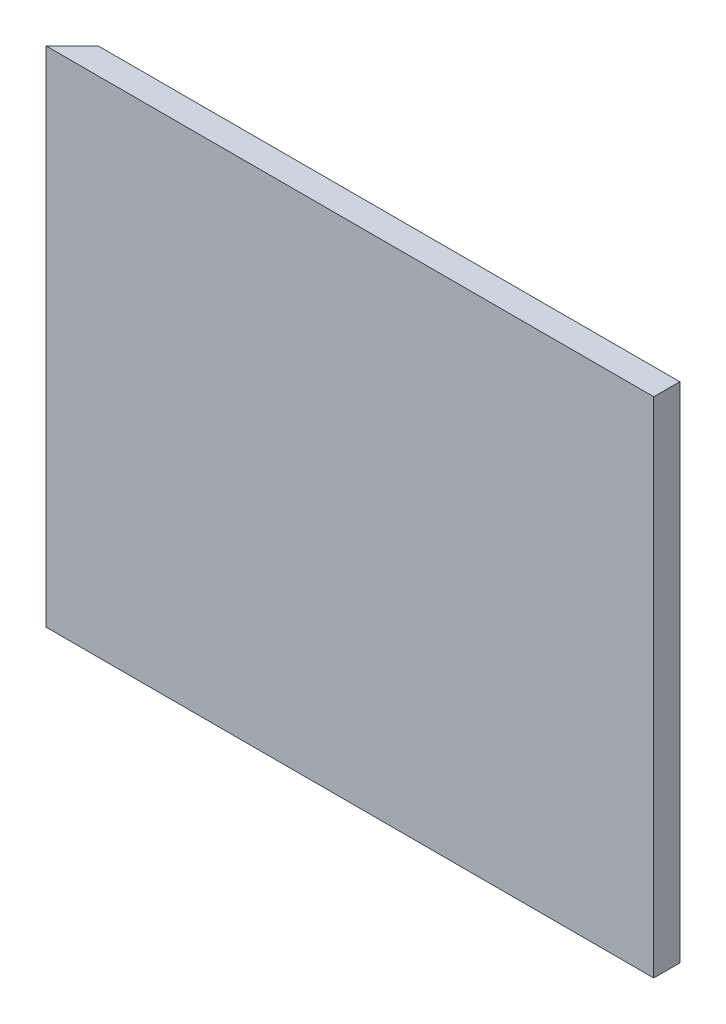
SolidWorks part; units mm, degrees
ref_plane "Top plane" through (0, 0, 0) normal (0, 0, 1) x (1, 0, 0)
ref_plane "Right plane" through (0, 0, 0) normal (0, 1, 0) x (1, 0, 0)
ref_plane "Front plane" through (0, 0, 0) normal (1, 0, 0) x (0, 0, -1)
sketch "Sketch1" plane through (0, 0, 0) normal (0, 0, 1) x (1, 0, 0)
  line L1 (-90.3791, 110.9772) -> (-160.3791, 110.9772)
  line L2 (-90.3791, 110.9772) -> (-90.3791, 52.9772)
  line L3 (-90.3791, 52.9772) -> (-160.3791, 52.9772)
  line L4 (-160.3791, 110.9772) -> (-160.3791, 52.9772)
  point P4 (-144.2066, 84.5291)
  point P5 (-144.2066, 177.0724)
  point P6 (-90.3791, 52.9772)
  point P7 (-90.3791, 110.9772)
  dimension "D1" = 70
extrude "Boss-Extrude1" add sketch "Sketch1" along normal blind 3
chamfer "Chamfer1" distance 3 angle 45 1 edges at (-160.3791, 81.9772, 0)
